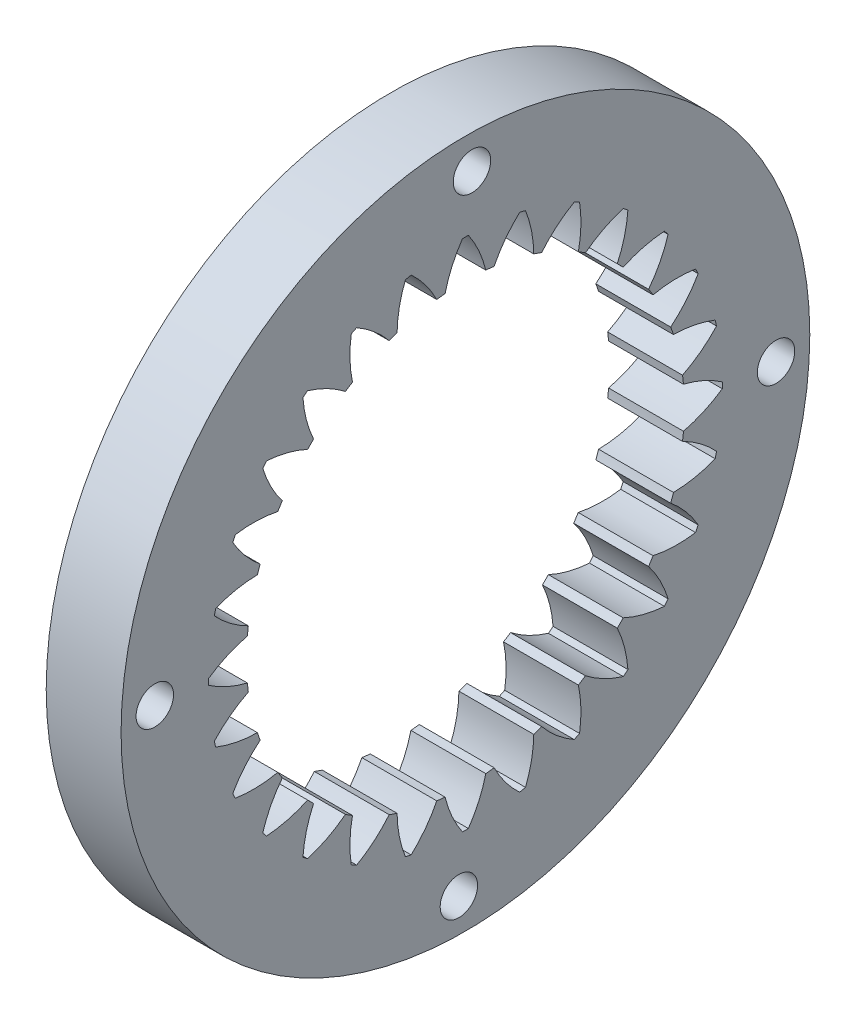
SolidWorks part; units mm, degrees
ref_plane "Plane1" through (0, 0, 0) normal (0, 0, 1) x (1, 0, 0)
ref_plane "Plane2" through (0, 0, 0) normal (0, 1, 0) x (1, 0, 0)
ref_plane "Plane3" through (0, 0, 0) normal (1, 0, 0) x (0, 0, -1)
sketch "HoldingSke" plane through (0, 0, 0) normal (0, 1, 0) x (1, 0, 0)
  line L0 (0, 0) -> (0.3924, -0.2087)
  line L1 (-15, 0) -> (100, 0) construction
  line L2 (0, 0) -> (-2.1039, 2.3779)
  line L3 (0, 0) -> (-11.863, 4.5341)
  line L4 (0, 0) -> (7.6251, 4.0544)
  line L5 (0, 0) -> (-23.7986, -8.8762)
  line L6 (0, 0) -> (-10.5278, -7.1032)
  line L7 (-2.1039, 2.3779) -> (3.3635, 27.1825)
  line L8 (-76.2, 4.6279) -> (-54.61, 4.6279)
  line L9 (-71.009, 38.7566) -> (-53.1078, 45.2721)
  line L10 (-76.2, 71.12) -> (104.1128, 71.12)
  line L11 (0, 0) -> (-10, 0)
  line L12 (-76.2, 101.6) -> (-76.123, 101.6)
  line L13 (24.9733, 27.94) -> (52.9518, 28.4284)
  line L14 (24.9733, 27.94) -> (24.9743, 27.94)
  line L15 (24.9733, 27.94) -> (100.4006, 29.5858)
  circle A0 centre (0, 0) radius 46
  circle A1 centre (0, 0) radius 12.7
  circle A2 centre (0, 0) radius 12.7
  dimension "Num_teeth" = 28
  dimension "Pitch_radius" = 180.3128
  dimension "Width" = 10
  dimension "Diameter" = 92
sketch "BasProSke" plane through (0, 0, 0) normal (0, 1, 0) x (1, 0, 0)
  line L0 (-10, 0) -> (60, 0) construction
  line L1 (0, 29.25) -> (0, 46)
  line L2 (0, 29.25) -> (10, 29.25)
  line L3 (10, 29.25) -> (10, 46)
  line L4 (10, 46) -> (0, 46)
  dimension "Thickness" = 10
  dimension "Diameter" = 92
revolve "Base-Revolve" add sketch "BasProSke" angle 360 about L0
sketch "TooCutSke" plane through (0, 0, 0) normal (1, 0, 0) x (0, 0, -1)
  line L3 (1.9587, 31.439) -> (1.9587, 53.6633) construction
  line L4 (0, 0) -> (0, 59.563) construction
  line L5 (0, 0) -> (-7.6503, 67.8979) construction
  line L6 (-12.5838, 25.391) -> (34.6221, 30.7098) construction
  circle A0 centre (0, 0) radius 31.5 construction
  circle A1 centre (0, 0) radius 34.3135 construction
  circle A2 centre (0, 0) radius 26.6403 construction
  circle A3 centre (0, 0) radius 29.2246 construction
  arc A4 (2.7239, 29.0974) -> (0.3967, 34.3112) centre (-12.5838, 25.391) ccw
  arc A5 (2.7239, 29.0974) -> (-2.7239, 29.0974) centre (0, 0) ccw
  arc A6 (0.3967, 34.3112) -> (-0.3967, 34.3112) centre (0, 0) ccw
  arc A7 (-0.3967, 34.3112) -> (-2.7239, 29.0974) centre (12.5838, 25.391) ccw
extrude "ToothCut" cut sketch "TooCutSke" along normal through all
fillet "Breaks" [suppressed] radius 0.225
fillet "RootFillets" [suppressed] radius 0.5635
pattern_circular "TeethCuts" count 28 every 12.857 about axis through (-10, 0, 0) along (1, 0, 0) of "RootFillets", "Breaks", "ToothCut"
sketch "Sketch1" plane through (0, 0, 0) normal (-1, 0, 0) x (0, 0, 1)
  circle A0 centre (41.4908, 0.8726) radius 2.5
  circle A1 centre (0.8726, -41.4908) radius 2.5
  circle A2 centre (-41.4908, -0.8726) radius 2.5
  circle A3 centre (-0.8726, 41.4908) radius 2.5
extrude "Cut-Extrude1" cut sketch "Sketch1" against normal blind 10
equation "' \"Module@HoldingSke\" = 6.35"
equation "' \"Num_teeth@HoldingSke\" = 24"
equation "' \"Ap@HoldingSke\" =  14.5"
equation "' \"Ap@HoldingSke\" = 14.5"
equation "' \"Width@HoldingSke\" = 12"
equation "' \"Diameter@HoldingSke\" = 8 * 25.4"
equation "' \"Show_teeth@HoldingSke\" = 100"
equation "' \"Backlash@HoldingSke\" = 0.009 * 25.4"
equation "' \"Addendum_fac@HoldingSke\" = 1.0"
equation "' \"Dedendum_fac@HoldingSke\" = 1.25"
equation "' \"Dedendum_add@HoldingSke\" = 0.00005 * 25.4"
equation "' \"Clearance_fac@HoldingSke\" = 0.25"
equation "\"Pitch@HoldingSke\" = 1 / \"Module@HoldingSke\" "
equation "\"Overcut_dia@TooCutSke\" = (\"Num_teeth@HoldingSke\" - 2 * \"Addendum_fac@HoldingSke\") / \"Pitch@HoldingSke\" - 0.002 * 25.4"
equation "\"Pitch_dia@TooCutSke\" = \"Num_teeth@HoldingSke\" / \"Pitch@HoldingSke\""
equation "\"Base_dia@TooCutSke\" = \"Num_teeth@HoldingSke\" / \"Pitch@HoldingSke\" * cos((\"Ap@HoldingSke\"  * 3.14159265 / 180)) * 0.90"
equation "\"Root_dia@TooCutSke\" = \"Num_teeth@HoldingSke\"  / \"Pitch@HoldingSke\" + 2 *  \"Dedendum_fac@HoldingSke\"/ \"Pitch@HoldingSke\" + \"Dedendum_add@HoldingSke\" * 2"
equation "\"Half_ang@TooCutSke\" = 180 / \"Num_teeth@HoldingSke\""
equation "\"Half_CT@TooCutSke\" = \"Num_teeth@HoldingSke\" / \"Pitch@HoldingSke\" * sin((3.14159265 / 2 / \"Num_teeth@HoldingSke\")) / 2 + 10 * \"Backlash@HoldingSke\" / 4"
equation "\"Flank_rad@TooCutSke\" = \"Num_teeth@HoldingSke\" / \"Pitch@HoldingSke\" / 4"
equation "\"Radius@RootFillets\"= \"Clearance_fac@HoldingSke\" / \"Pitch@HoldingSke\" + \"Dedendum_add@HoldingSke\""
equation "\"Break_rad@Breaks\" = 0.02 / \"Pitch@HoldingSke\" * 5"
equation "\"Num_teeth@TeethCuts\" = int( \"Show_teeth@HoldingSke\" ) + 1"
equation "\"Num_teeth@TeethCuts\" = ((sgn( \"Num_teeth@TeethCuts\" - \"Num_teeth@HoldingSke\" )-1)*( \"Num_teeth@TeethCuts\" - \"Num_teeth@HoldingSke\" ))/-2+ \"Num_teeth@HoldingSke\""
equation "\"Num_teeth@TeethCuts\" = ((sgn( \"Num_teeth@TeethCuts\" - 2.0)+1)*( \"Num_teeth@TeethCuts\" - 2.0))/2 +2.0"
equation "\"Angle@TeethCuts\" = 360.0 / \"Num_teeth@HoldingSke\""
equation "\"Diameter@BasProSke\" = \"Num_teeth@HoldingSke\"  / \"Pitch@HoldingSke\" + 2 *  \"Dedendum_fac@HoldingSke\"/ \"Pitch@HoldingSke\" + \"Dedendum_add@HoldingSke\" * 2 + 0.002 * 25.4"
equation "\"Diameter@BasProSke\" = ((sgn( \"Diameter@BasProSke\"  - \"Diameter@HoldingSke\" )+1)*( \"Diameter@BasProSke\"  - \"Diameter@HoldingSke\" ))/2 + \"Diameter@HoldingSke\""
equation "\"Inside_diameter@BasProSke\" =  (\"Num_teeth@HoldingSke\" - 2 * \"Addendum_fac@HoldingSke\") / \"Pitch@HoldingSke\" "
equation "\"Thickness@BasProSke\"  = \"Width@HoldingSke\""
